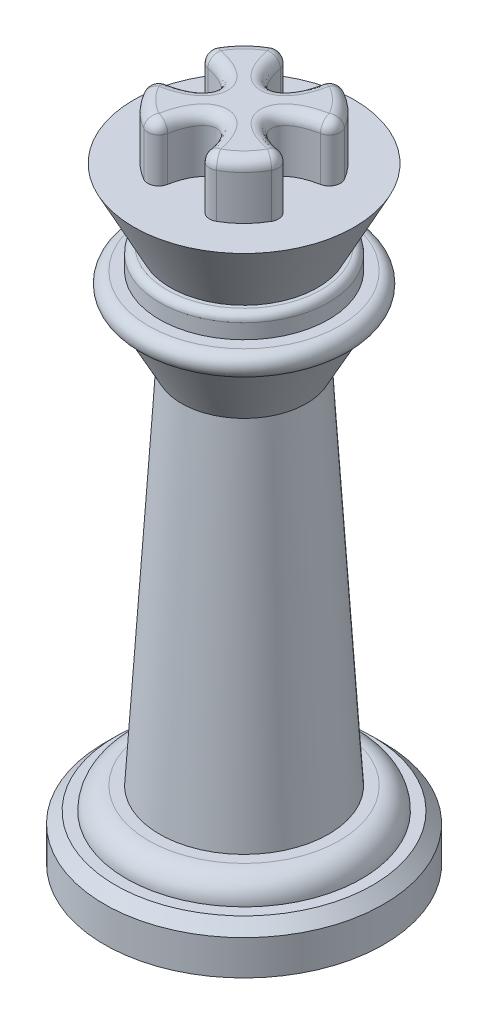
SolidWorks part; units mm, degrees
ref_plane "Front Plane" through (0, 0, 0) normal (0, 0, 1) x (1, 0, 0)
ref_plane "Top Plane" through (0, 0, 0) normal (0, 1, 0) x (1, 0, 0)
ref_plane "Right Plane" through (0, 0, 0) normal (1, 0, 0) x (0, 0, -1)
sketch "Sketch1" plane through (0, 0, 0) normal (0, 0, 1) x (1, 0, 0)
  line L0 (0, 0) -> (0, 45.72) construction
  line L1 (0, 0) -> (-9.652, 0)
  line L3 (-8.128, 3.175) -> (-9.652, 3.175)
  line L4 (-9.652, 0) -> (-9.652, 3.175)
  line L7 (-5.842, 4.699) -> (-8.128, 4.699)
  line L8 (-8.128, 3.175) -> (-8.128, 4.699)
  line L9 (-5.842, 4.699) -> (-4.318, 29.7074)
  line L10 (-4.318, 29.7074) -> (-6.604, 33.9683)
  line L11 (-6.604, 35.4923) -> (-5.842, 35.4923)
  line L16 (-5.842, 35.4923) -> (-5.842, 37.0163)
  line L17 (-5.842, 37.0163) -> (-5.08, 37.0163)
  line L18 (-5.08, 37.0163) -> (-7.62, 41.91)
  line L19 (0, 0) -> (0, 45.72)
  line L20 (0, 45.72) -> (-5.08, 45.72)
  line L21 (-5.08, 45.72) -> (-5.08, 41.91)
  line L22 (-5.08, 41.91) -> (-7.62, 41.91)
  arc A1 (-6.604, 35.4923) -> (-6.604, 33.9683) centre (-6.604, 34.7303) ccw
  point P25 (-7.0701, 36.3947)
  dimension "D10" = 1.524
  dimension "D1" = 9.652
  dimension "D2" = 3.175
  dimension "D3" = 1.524
  dimension "D4" = 1.524
  dimension "D5" = 3.81
  dimension "D6" = 2.286
  dimension "D7" = 4.318
  dimension "D8" = 6.604
  dimension "D9" = 1.524
  dimension "D11" = 1.524
  dimension "D12" = 0.762
  dimension "D13" = 5.08
  dimension "D14" = 7.62
  dimension "D15" = 5.08
  dimension "D16" = 45.72
revolve "Revolve1" add sketch "Sketch1" angle 360 about L0
fillet "Fillet2" radius 1.524 1 edges at (0, 4.699, -8.128)
chamfer "Chamfer1" distance 0.762 angle 45 1 edges at (0, 3.175, -9.652)
fillet "Fillet3" radius 0.508 1 edges at (0, 37.0163, -5.842)
sketch "Sketch2" plane through (0, 45.72, 0) normal (0, 1, 0) x (1, 0, 0)
  circle A0 centre (0, 0) radius 5.08 construction
  circle A1 centre (0, 0) radius 5.08 construction
  ellipse E0 centre (0, 5.08) end of major axis (0, 8.2647) minor radius 1.4951
  ellipse E1 centre (5.08, 0) end of major axis (1.8953, 0) minor radius 1.4951
  ellipse E2 centre (0, -5.08) end of major axis (0, -8.2647) minor radius 1.4951
  ellipse E3 centre (-5.08, 0) end of major axis (-8.2647, 0) minor radius 1.4951
  point P31 (0, 0)
  dimension "D1" = 4
extrude "Cut-Extrude1" cut sketch "Sketch2" against normal up to surface (3.81 mm away) up to face at (0, 41.91, -7.62)
fillet "Fillet4" radius 0.762 16 edges at (1.8953, 45.72, 0) (3.5921, 45.72, 3.5921) (0, 45.72, 1.8953) (-3.5921, 45.72, 3.5921) (-1.8953, 45.72, 0) (-3.5921, 45.72, -3.5921) (0, 45.72, -1.8953) (3.5921, 45.72, -3.5921) (-4.8561, 43.815, -1.4914) (-4.8561, 43.815, 1.4914) (-1.4914, 43.815, 4.8561) (4.8561, 43.815, 1.4914) (4.8561, 43.815, -1.4914) (1.4914, 43.815, -4.8561) (-1.4914, 43.815, -4.8561) (1.4914, 43.815, 4.8561)
